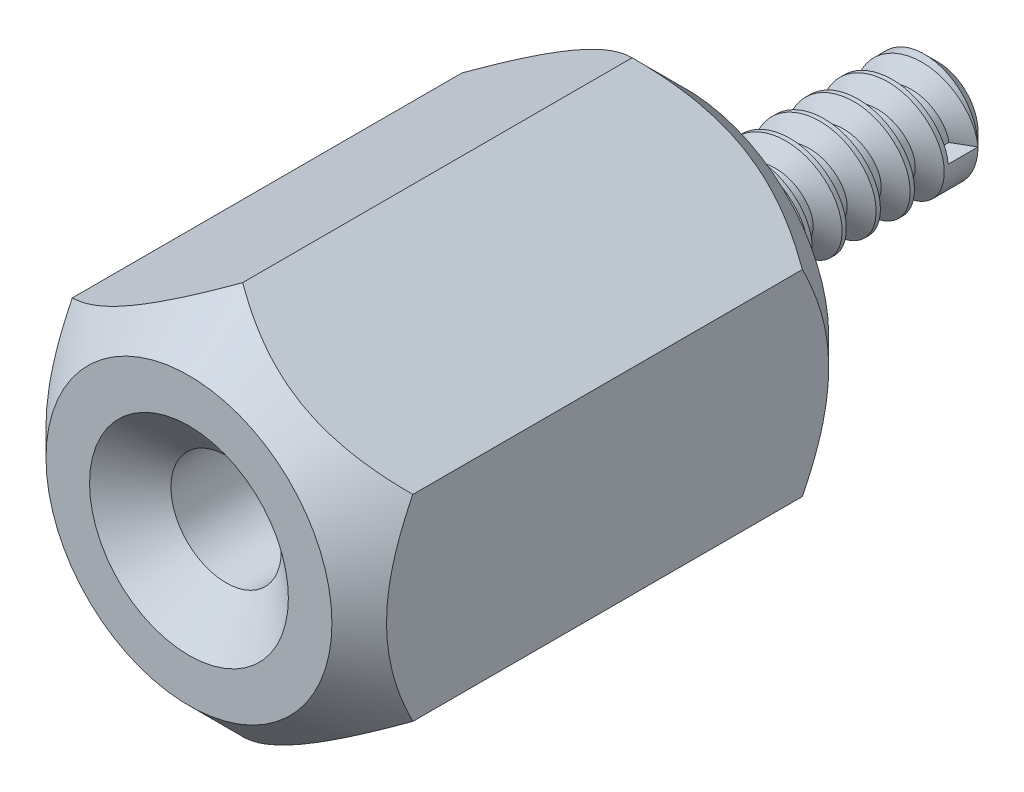
SolidWorks part; units mm, degrees
ref_plane "Front Plane" through (0, 0, 0) normal (0, 0, 1) x (1, 0, 0)
ref_plane "Top Plane" through (0, 0, 0) normal (0, 1, 0) x (1, 0, 0)
ref_plane "Right Plane" through (0, 0, 0) normal (1, 0, 0) x (0, 0, -1)
sketch "Sketch1" plane through (0, 0, 0) normal (0, 0, 1) x (1, 0, 0)
  line L1 (3.175, -1.8331) -> (3.175, 1.8331)
  line L2 (3.175, 1.8331) -> (0, 3.6662)
  line L3 (0, 3.6662) -> (-3.175, 1.8331)
  line L4 (-3.175, 1.8331) -> (-3.175, -1.8331)
  line L5 (-3.175, -1.8331) -> (0, -3.6662)
  line L6 (0, -3.6662) -> (3.175, -1.8331)
  circle A0 centre (0, 0) radius 3.175 construction
  dimension "D1" = 6.35
extrude "Boss-Extrude1" add sketch "Sketch1" along normal blind 4.6325 and the other way blind 4.6325
ref_axis "Axis1" through (0, 0, -0.635) along (0, 0, 1)
sketch "Sketch3" plane through (0, 0, 0) normal (1, 0, 0) x (0, 0, -1)
  line L0 (-4.6325, 3.6662) -> (4.6325, 3.6662) construction
  line L1 (-3.6325, 3.6662) -> (-4.6325, 2.6662)
  line L2 (-4.6325, 1.8331) -> (-4.6325, 3.6662) construction
  line L3 (-4.6325, 2.6662) -> (-4.6325, 3.6662)
  line L4 (-4.6325, 3.6662) -> (-3.6325, 3.6662)
  dimension "D1" = 1
  dimension "D2" = 45
revolve "Cut-Revolve2" cut sketch "Sketch3" angle 360 about axis through (0, 0, -0.635) along (0, 0, 1)
mirror "Mirror1" about plane through (0, 0, 0) normal (0, 0, 1) of "Cut-Revolve2"
hole_wizard "CSK for #1 Flat Head Machine Screw (100)1" positions "Sketch5" profile "Sketch4" countersink size "#1" standard "ANSI Inch"
sketch "Sketch5" plane through (0, 0, 4.6325) normal (0, 0, 1) x (1, 0, 0)
  point P0 (0, 0)
sketch "Sketch4" plane through (0, 0, 4.6325) normal (1, 0, 0) x (0, -1, 0)
  line L0 (0, 0) -> (0, 10.6181)
  line L1 (0, 10.6181) -> (1.0287, 10)
  line L2 (1.0287, 10) -> (1.0287, 0.6927)
  line L3 (1.0287, 0.6927) -> (1.8542, 0)
  line L5 (1.8542, 0) -> (0, 0)
  line L6 (-1.0287, 0.6927) -> (-1.8542, 0) construction
  line L10 (0, 10.6181) -> (-1.0287, 10) construction
  line L11 (0, -6.35) -> (0, 107.95) construction
  dimension "Hole Dia." = 2.0574
  dimension "Hole Depth" = 10
  dimension "Near C'Sink Dia." = 3.7084
  dimension "Near C'Sink Angle" = 100
  dimension "Drill Angle" = 118
sketch "Sketch6" plane through (0, 0, -4.6325) normal (0, 0, -1) x (-1, 0, 0)
  circle A0 centre (0, 0) radius 1
  dimension "D1" = 2
extrude "Boss-Extrude2" add sketch "Sketch6" along normal blind 4.7
chamfer "Chamfer1" distance 0.25 angle 45 1 edges at (-1, 0, -9.3325)
thread "Thread1" pitch 0.635 method cut profile "Thread Profile1" start angle 0, offset 0, length 4, pitch 0.635, diameter 2
ref_plane "Plane1" through (1, 0, -9.0825) normal (0, -1, 0) x (1, 0, 0)
sketch "Thread Profile1" plane through (1, 0, -9.0825) normal (0, -1, 0) x (1, 0, 0)
  line L0 (0, 0) -> (0, 0.635) construction
  line L11 (0, 0) -> (0, 0.5556)
  line L12 (0, 0.5556) -> (-0.3437, 0.3572)
  line L13 (-0.3437, 0.3572) -> (-0.3437, 0.1984)
  line L15 (-0.3437, 0.1984) -> (0, 0)
  line L17 (-0.3437, 0.2778) -> (0, 0.2778) construction
  point P2 (0, 0)
  dimension "Pitch" = 0.635
  dimension "Profile_Angle" = 60
  dimension "Profile_Land" = 0.1588
  dimension "Profile_Height" = 0.3437
